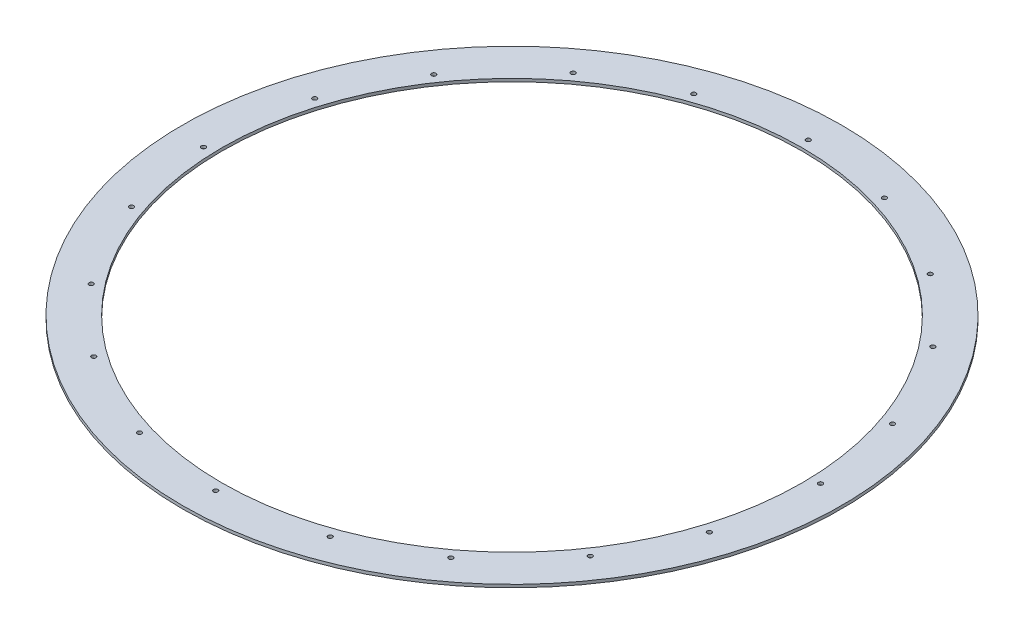
SolidWorks part; units mm, degrees
ref_plane "Front Plane" through (0, 0, 0) normal (0, 0, 1) x (1, 0, 0)
ref_plane "Top Plane" through (0, 0, 0) normal (0, 1, 0) x (1, 0, 0)
ref_plane "Right Plane" through (0, 0, 0) normal (1, 0, 0) x (0, 0, -1)
sketch "Sketch1" plane through (0, 0, 0) normal (0, 1, 0) x (1, 0, 0)
  circle A0 centre (0, 0) radius 295
  circle A1 centre (0, 0) radius 335
  dimension "D1" = 590
  dimension "D2" = 670
extrude "Boss-Extrude1" add sketch "Sketch1" along normal blind 3
hole_wizard "CBORE for M4 SHCS1" positions "Sketch2" profile "Sketch3" counterbore size "M4" standard "ANSI Metric"
sketch "Sketch2" plane through (-17.8059, 23, -255.0543) normal (0, 1, 0) x (0.3446, 0, -0.9388)
  line L0 (-9.1258, -311.4157) -> (-233.2982, -104.6025) construction
  point P0 (24.7685, -267.1649)
  point P4 (61.1274, -184.2176)
  point P32 (-120.0697, -387.8061)
  point P34 (-41.8995, -342.0715)
  point P35 (-308.1573, -400.2731)
  point P37 (-218.0342, -409.2203)
  point P38 (-467.6513, -299.804)
  point P40 (-399.9992, -360.0154)
  point P41 (-537.6304, -124.7745)
  point P43 (-518.2901, -213.2515)
  point P44 (-491.365, 57.96)
  point P46 (-527.7238, -24.9874)
  point P47 (-346.5268, 178.6011)
  point P49 (-424.697, 132.8665)
  point P50 (-158.4392, 191.0681)
  point P52 (-248.5623, 200.0153)
  point P53 (1.0549, 90.599)
  point P55 (-66.5972, 150.8105)
  point P56 (71.034, -84.4304)
  point P58 (51.6937, 4.0466)
  point P59 (-233.2982, -104.6025)
sketch "Sketch3" plane through (241.5317, 23, -186.2457) normal (1, 0, 0) x (0, 0, 1)
  line L0 (0, 0) -> (0, 32.3519)
  line L1 (0, 32.3519) -> (2.25, 31)
  line L2 (2.25, 31) -> (2.25, 4)
  line L3 (2.25, 4) -> (4, 4)
  line L4 (4, 4) -> (4, 0)
  line L5 (4, 0) -> (0, 0)
  line L6 (0, 32.3519) -> (-2.25, 31) construction
  line L7 (0, -6.35) -> (0, 107.95) construction
  dimension "Hole Dia." = 4.5
  dimension "Hole Depth" = 31
  dimension "C'Bore Dia." = 8
  dimension "C'Bore Depth" = 4
  dimension "Drill Angle" = 118
